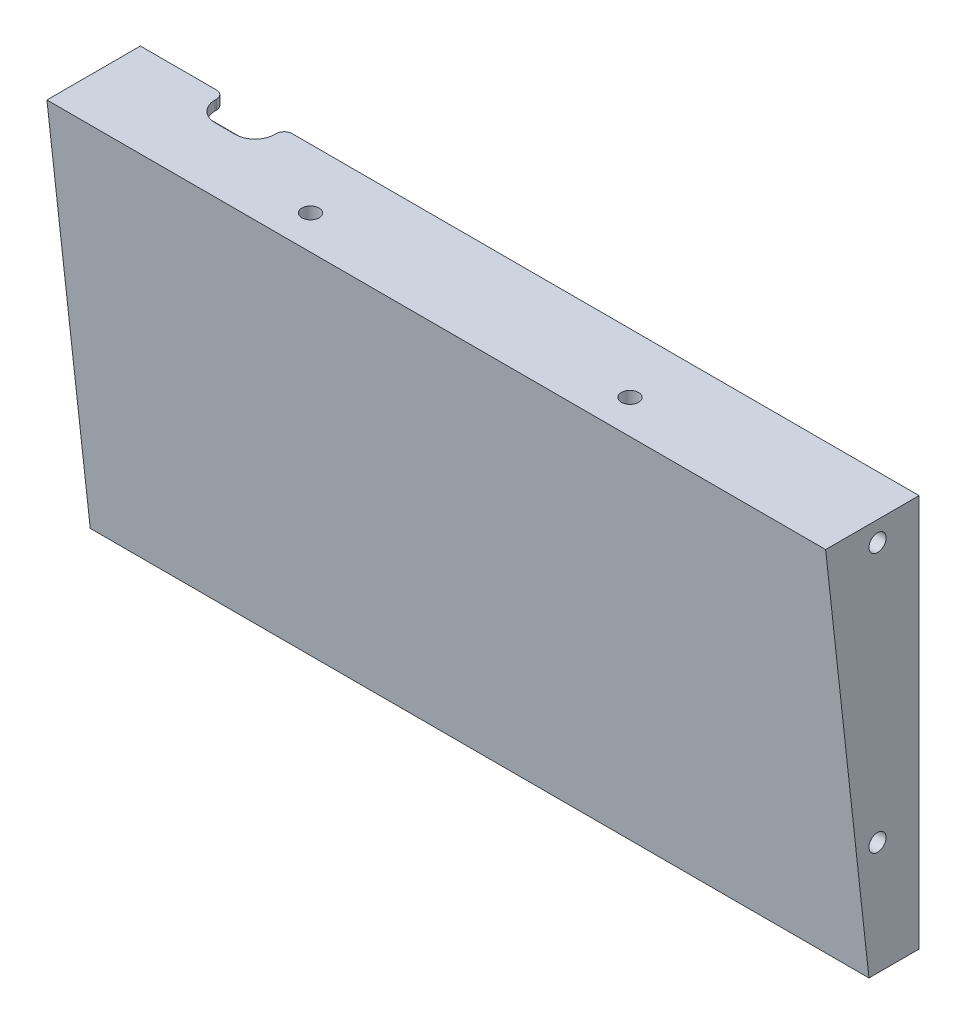
SolidWorks part; units mm, degrees
note: The reader was unsure of these and kept them because the rebuilt part matched: shared geometry of "Sketch1<3>", "Sketch1<4>", "Sketch6<2>", "Sketch1<5>", "Sketch7<2>".
ref_plane "Front Plane" through (0, 0, 0) normal (0, 0, 1) x (1, 0, 0)
ref_plane "Top Plane" through (0, 0, 0) normal (0, 1, 0) x (1, 0, 0)
ref_plane "Right Plane" through (0, 0, 0) normal (1, 0, 0) x (0, 0, -1)
sketch "Sketch1" plane through (0, 0, 0) normal (0, 0, 1) x (1, 0, 0)
  line L0 (92.2873, 29.0011) -> (86.4373, 29.0011) construction
  line L1 (-94.888, 46.5645) -> (94.888, 46.5645)
  line L2 (-94.888, 46.5645) -> (-94.888, -46.5645)
  line L3 (-94.888, -46.5645) -> (94.888, -46.5645)
  line L4 (94.888, 46.5645) -> (94.888, -46.5645)
  line L5 (-97.488, 49.1645) -> (97.488, 49.1645)
  line L6 (-97.488, 49.1645) -> (-97.488, -49.1645)
  line L7 (-97.488, -49.1645) -> (97.488, -49.1645)
  line L8 (97.488, 49.1645) -> (97.488, -49.1645)
  line L9 (-87.888, 44.0645) -> (91.888, 44.0645)
  line L10 (-87.888, 44.0645) -> (-87.888, -40.5645)
  line L11 (-87.888, -40.5645) -> (91.888, -40.5645)
  line L12 (91.888, 44.0645) -> (91.888, -40.5645)
  line L13 (91.888, 31.0011) -> (94.888, 31.0011)
  line L14 (91.888, 31.0011) -> (91.888, 24.6011)
  line L15 (91.888, 24.6011) -> (94.888, 24.6011)
  line L16 (94.888, 31.0011) -> (94.888, 24.6011)
  line L17 (91.888, 11.9511) -> (94.888, 11.9511)
  line L18 (91.888, 11.9511) -> (91.888, 5.5511)
  line L19 (91.888, 5.5511) -> (94.888, 5.5511)
  line L20 (94.888, 11.9511) -> (94.888, 5.5511)
  line L21 (91.888, -7.1989) -> (94.888, -7.1989)
  line L22 (91.888, -7.1989) -> (91.888, -13.4989)
  line L23 (91.888, -13.4989) -> (94.888, -13.4989)
  line L24 (94.888, -7.1989) -> (94.888, -13.4989)
  line L25 (91.888, -26.1489) -> (94.888, -26.1489)
  line L26 (91.888, -26.1489) -> (91.888, -32.5489)
  line L27 (91.888, -32.5489) -> (94.888, -32.5489)
  line L28 (94.888, -26.1489) -> (94.888, -32.5489)
  line L29 (92.2873, 26.6011) -> (89.7373, 26.6011) construction
  line L30 (92.2873, 9.9511) -> (86.4373, 9.9511) construction
  line L31 (92.2873, 7.5511) -> (89.7373, 7.5511) construction
  line L32 (92.2873, -11.4989) -> (89.7373, -11.4989) construction
  line L33 (89.7373, -9.1989) -> (92.2873, -9.1989) construction
  line L34 (92.2873, -28.1489) -> (86.4373, -28.1489) construction
  line L35 (92.2873, -30.5489) -> (89.7373, -30.5489) construction
  line L36 (-94.488, 46.1645) -> (-94.488, -46.1645) construction
  line L37 (94.488, 46.1645) -> (-94.488, 46.1645) construction
  line L38 (-94.488, -46.1645) -> (94.488, -46.1645) construction
  line L39 (94.488, -46.1645) -> (94.488, 46.1645) construction
  arc A0 (64.0468, 44.0645) -> (69.2672, 44.0645) centre (66.657, 41.0335) ccw
  circle A1 centre (-91.11, 26.5025) radius 2.15
  circle A2 centre (-91.11, -43.4975) radius 2.15
  circle A3 centre (0.203, -43.4975) radius 2.15
  circle A4 centre (91.389, -43.4975) radius 2.15
  circle A5 centre (66.657, 41.0335) radius 2.15
  point P10 (0, 46.5645)
  point P11 (0, 49.1645)
  point P12 (97.488, 0)
  point P13 (94.888, 0)
  point P48 (93.388, -32.5489)
  dimension "D15" = 4
  dimension "D16" = 4.3
  dimension "D17" = 4.3
  dimension "D18" = 4.3
  dimension "D19" = 4.3
  dimension "D20" = 4.3
  dimension "D3" = 2.5
  dimension "D4" = 7
  dimension "D5" = 6
  dimension "D6" = 3
  dimension "D7" = 2
  dimension "D8" = 2
  dimension "D9" = 2
  dimension "D10" = 2
  dimension "D11" = 2
  dimension "D12" = 2
  dimension "D13" = 2
  dimension "D14" = 2
  dimension "D21" = 194.976
  dimension "D22" = 98.329
  dimension "D23" = 0.4
  dimension "D24" = 0.4
  dimension "D25" = 0.4
  dimension "D26" = 0.4
extrude "Boss-Extrude1" add sketch "Sketch1" along normal offset from surface (3.1509 mm away) 1.3 contours L27 L12 L11 L10 L9 L13 L4 L1 L2 L3 A4 A3 A2 A1 | L12 L17 L4 L15 | L12 L21 L4 L19 | L12 L25 L4 L23 | L9 A0 A5
extrude "Boss-Extrude2" add sketch "Sketch1<3>" along normal blind 3 from surface at 3.1509 contours L27 L12 L11 L10 L9 L13 L4 L1 L2 L3 A4 A3 A2 A1 | L12 L19 L4 L17 | L12 L17 L4 L15 | A0 L9 L10 L11 L12 | L12 L21 L4 L19 | L12 L23 L4 L21 | L12 L25 L4 L23 | L12 L27 L4 L25 | L12 L15 L4 L13 | L9 A0 A5 | A5 | A4 | A3 | A2 | A1 starting at face at (36.7761, 6.0716, 3.1509)
sketch "Sketch1<3>" plane through (0, 0, 0) normal (0, 0, 1) x (1, 0, 0) same geometry as "Sketch1"
extrude "Boss-Extrude4" add sketch "Sketch1<4>" along normal up to surface (6.1509 mm away) contours L8 L5 L6 L7 L1 L4 L3 L2 up to face at (0, 0, 6.1509)
sketch "Sketch1<4>" plane through (0, 0, 0) normal (0, 0, 1) x (1, 0, 0) same geometry as "Sketch1"
sketch "Sketch4" plane through (-97.488, 0, 0) normal (-1, 0, 0) x (0, 0, 1)
  line L0 (6.1509, 49.1645) -> (17, 49.1645)
  line L1 (17, 49.1645) -> (6.1509, -49.1645)
  line L2 (6.1509, -49.1645) -> (6.1509, 49.1645)
  dimension "D1" = 17
extrude "Boss-Extrude5" add sketch "Sketch4" against normal up to surface (194.976 mm away) up to face at (97.488, 0, 3.0754)
sketch "Sketch5" plane through (0, 49.1645, 0) normal (0, 1, 0) x (1, 0, 0)
  line L0 (-97.488, -17) -> (-97.488, 0) construction
  line L1 (-40, -8.5) -> (40, -8.5) construction
  line L2 (-97.488, 0) -> (97.488, 0) construction
  circle A0 centre (-40, -8.5) radius 2.15
  circle A1 centre (40, -8.5) radius 2.15
  point P7 (-97.488, -8.5)
  point P9 (0, 0)
  point P10 (0, -8.5)
  dimension "D2" = 4.3
  dimension "D3" = 4.3
  dimension "D1" = 80
extrude "Cut-Extrude2" cut sketch "Sketch5" against normal blind 4
sketch "Sketch6" plane through (97.488, 0, 0) normal (1, 0, 0) x (0, 0, -1)
  line L0 (-17, 49.1645) -> (0, 49.1645) construction
  line L1 (0, 49.1645) -> (0, -49.1645) construction
  circle A0 centre (-4, 44.1645) radius 2.15
  circle A1 centre (-4, -20.8355) radius 2.15
  dimension "D1" = 4.3
  dimension "D2" = 4.3
  dimension "D3" = 65
  dimension "D4" = 5
  dimension "D5" = 4
extrude "Cut-Extrude3" cut sketch "Sketch6" against normal blind 4
extrude "Cut-Extrude4" cut sketch "Sketch6<2>" along normal blind 4 from surface at -194.976 starting at face at (-97.488, 0, 5.7877)
sketch "Sketch6<2>" plane through (97.488, 0, 0) normal (1, 0, 0) x (0, 0, -1) same geometry as "Sketch6"
extrude "Boss-Extrude6" add sketch "Sketch1<5>" against normal up to surface (1.6 mm away) contours L8 L5 L6 L7 L1 L4 L3 L2
sketch "Sketch1<5>" plane through (0, 0, 0) normal (0, 0, 1) x (1, 0, 0) same geometry as "Sketch1"
sketch "Sketch7" plane through (-97.488, 0, 0) normal (-1, 0, 0) x (0, 0, 1)
  circle A0 centre (-3.6, 40.4495) radius 3
  dimension "D1" = 6
extrude "Cut-Extrude5" cut sketch "Sketch7" against normal up to surface (2.6 mm away) up to face at (-94.888, 0, -0.8)
extrude "Cut-Extrude6" cut sketch "Sketch7<2>" against normal up to surface (2.6 mm away) from surface
sketch "Sketch7<2>" plane through (-97.488, 0, 0) normal (-1, 0, 0) x (0, 0, 1) same geometry as "Sketch7"
sketch "Sketch9" plane through (0, 0, -1.6) normal (0, 0, -1) x (-1, 0, 0)
  line L0 (97.488, 49.1645) -> (-97.488, 49.1645) construction
  line L1 (-97.488, 42.6856) -> (-95.088, 42.6856)
  line L2 (-97.488, 42.6856) -> (-97.488, 49.1645)
  line L3 (-97.488, 49.1645) -> (-95.088, 49.1645)
  line L4 (-95.088, 42.6856) -> (-95.088, 49.1645)
  line L5 (97.488, 49.1645) -> (97.488, 42.6856) construction
  line L6 (-95.088, 49.1645) -> (97.488, 49.1645)
  line L7 (-95.088, 49.1645) -> (-95.088, 46.7645)
  line L8 (-95.088, 46.7645) -> (97.488, 46.7645)
  line L9 (97.488, 49.1645) -> (97.488, 46.7645)
  line L10 (97.488, 42.6856) -> (94.888, 42.6856) construction
  line L11 (97.488, 46.7645) -> (95.088, 46.7645)
  line L12 (97.488, 46.7645) -> (97.488, 42.6856)
  line L13 (97.488, 42.6856) -> (95.088, 42.6856)
  line L14 (95.088, 46.7645) -> (95.088, 42.6856)
  line L15 (97.488, -49.1645) -> (-97.488, -49.1645) construction
  line L16 (97.488, 38.2134) -> (95.088, 38.2134)
  line L17 (97.488, 38.2134) -> (97.488, -49.1645)
  line L18 (97.488, -49.1645) -> (95.088, -49.1645)
  line L19 (95.088, 38.2134) -> (95.088, -49.1645)
  line L20 (94.888, 46.5645) -> (94.888, 42.6856) construction
  line L21 (94.888, 46.5645) -> (-94.888, 46.5645) construction
  line L22 (-94.888, 46.5645) -> (-94.888, 42.6856) construction
  line L23 (94.888, -46.5645) -> (-94.888, -46.5645) construction
  line L24 (-97.488, 38.2134) -> (-95.088, 38.2134)
  line L25 (-97.488, 38.2134) -> (-97.488, -49.1645)
  line L26 (-97.488, -49.1645) -> (-95.088, -49.1645)
  line L27 (-95.088, 38.2134) -> (-95.088, -49.1645)
  line L28 (-95.088, -49.1645) -> (95.088, -49.1645)
  line L29 (-95.088, -49.1645) -> (-95.088, -46.7645)
  line L30 (-95.088, -46.7645) -> (95.088, -46.7645)
  line L31 (95.088, -49.1645) -> (95.088, -46.7645)
  line L33 (95.088, 42.6856) -> (97.488, 42.6856)
  line L34 (95.088, 42.6856) -> (95.088, 38.2134)
  line L35 (95.088, 38.2134) -> (97.488, 38.2134)
  line L36 (97.488, 42.6856) -> (97.488, 38.2134)
  line L37 (-97.488, 42.6856) -> (-95.088, 42.6856)
  line L38 (-97.488, 42.6856) -> (-97.488, 38.2134)
  line L39 (-97.488, 38.2134) -> (-95.088, 38.2134)
  line L40 (-95.088, 42.6856) -> (-95.088, 38.2134)
  line M22 (-97.488, 42.6856) -> (-94.888, 42.6856)
  line M26 (94.888, 42.6856) -> (97.488, 42.6856)
  line M27 (97.488, 42.6856) -> (97.488, 49.1645)
  line M28 (97.488, 49.1645) -> (-97.488, 49.1645)
  line M29 (-97.488, 49.1645) -> (-97.488, 42.6856)
  dimension "D1" = 0.2
  dimension "D2" = 0.2
  dimension "D3" = 0.2
  dimension "D4" = 0.2
extrude "Boss-Extrude7" add sketch "Sketch9" along normal up to surface (6.8 mm away) from offset 2 contours L4 M22 M28 M29 | L4 L8 M27 M28 | L27 L24 L25 L26 | L8 L14 M26 M27 | L16 L19 L18 L17 | L30 L27 L28 L19 | L40 L38 L24 M22 | L36 L34 L16 M26
sketch "Sketch10" plane through (0, 49.1645, 0) normal (0, 1, 0) x (1, 0, 0)
  line L0 (-71.4856, 4.055) -> (-66.4456, 4.055) construction
  line L1 (-71.4856, 9.005) -> (-66.4456, 9.005)
  line L2 (-71.4856, -0.895) -> (-66.4456, -0.895)
  line L4 (-65.7456, 6.005) -> (-72.1856, 6.005) construction
  line L7 (-73.1356, 2.105) -> (-73.4356, 2.105) construction
  line L8 (-76.4356, 4.055) -> (-76.4356, 6.4)
  line L9 (-97.488, 6.4) -> (97.488, 6.4) construction
  line L10 (-76.4356, 6.4) -> (-75.8449, 6.4)
  line L11 (-61.4956, 4.055) -> (-61.4956, 6.4)
  line L12 (-61.4956, 6.4) -> (-62.0863, 6.4)
  arc A0 (-71.4856, 9.005) -> (-71.4856, -0.895) centre (-71.4856, 4.055) ccw
  arc A1 (-66.4456, -0.895) -> (-66.4456, 9.005) centre (-66.4456, 4.055) ccw
  point P2 (-68.9656, 4.055)
  point P12 (-61.4956, 4.055)
  point P13 (-76.4356, 4.055)
  dimension "D1" = 3
  dimension "D2" = 3
  dimension "D3" = 3
  dimension "D4" = 3
extrude "Cut-Extrude7" cut sketch "Sketch10" against normal up to surface (2.4 mm away)
fillet "Fillet1" radius 2 2 edges at (-61.4956, 47.9645, -6.4) (-76.4356, 47.9645, -6.4)
